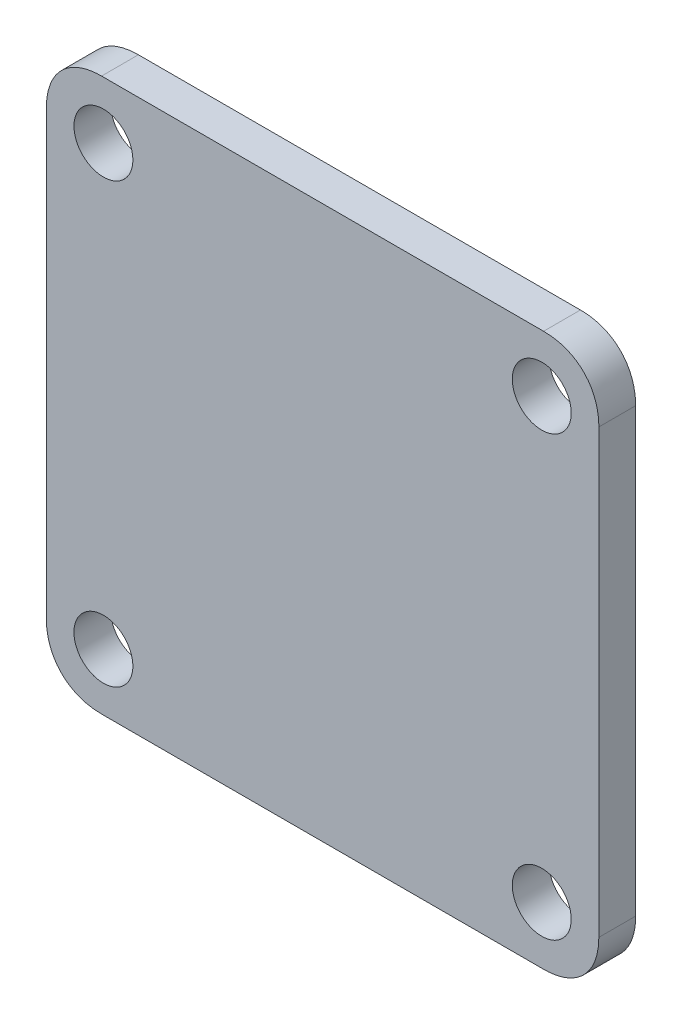
SolidWorks part; units mm, degrees
ref_plane "前视基准面" through (0, 0, 0) normal (0, 0, 1) x (1, 0, 0)
ref_plane "上视基准面" through (0, 0, 0) normal (0, 1, 0) x (1, 0, 0)
ref_plane "右视基准面" through (0, 0, 0) normal (1, 0, 0) x (0, 0, -1)
sketch "草图1" plane through (0, 0, 0) normal (0, 0, 1) x (1, 0, 0)
  line L0 (0, 0) -> (15, 0) construction
  line L1 (-15, 15) -> (15, 15)
  line L2 (-15, 15) -> (-15, -15)
  line L3 (-15, -15) -> (15, -15)
  line L4 (15, 15) -> (15, -15)
  line L5 (-15, 15) -> (15, -15) construction
  line L6 (-15, -15) -> (15, 15) construction
  line L7 (0, 0) -> (0, 15) construction
  circle A0 centre (-11.9, 11.9) radius 1.6
  circle A1 centre (11.9, 11.9) radius 1.6
  circle A2 centre (11.9, -11.9) radius 1.6
  circle A3 centre (-11.9, -11.9) radius 1.6
  point P0 (0, 0)
  dimension "D1" = 30
  dimension "D2" = 30
extrude "凸台-拉伸1" add sketch "草图1" along normal blind 2
fillet "圆角1" radius 3 4 edges at (-15, -15, 1) (15, -15, 1) (15, 15, 1) (-15, 15, 1) conic rho 0.45
